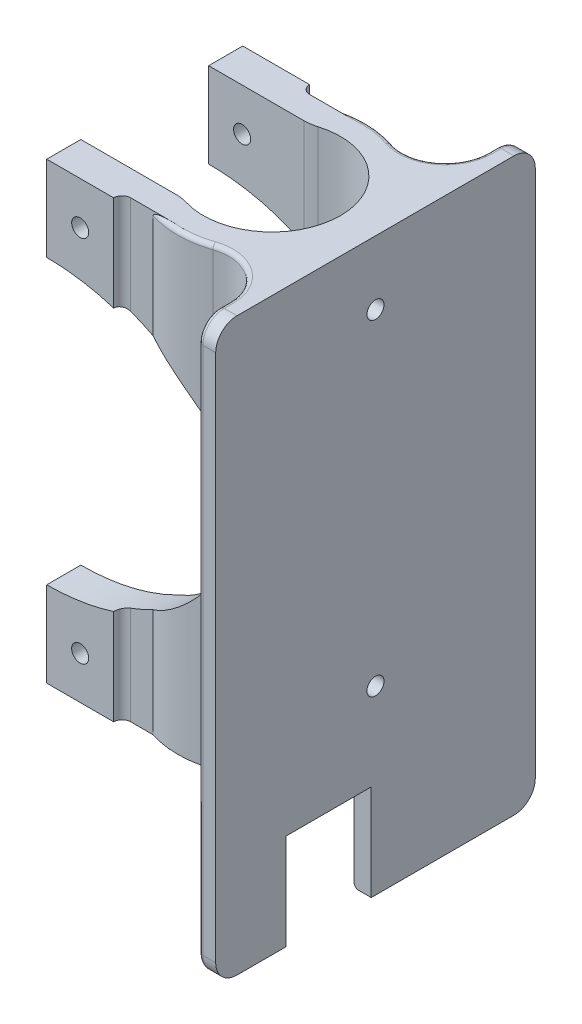
SolidWorks part; units mm, degrees
material "ABS"
ref_plane "Ebene vorne" through (0, 0, 0) normal (0, 0, 1) x (1, 0, 0)
ref_plane "Ebene oben" through (0, 0, 0) normal (0, 1, 0) x (1, 0, 0)
ref_plane "Ebene rechts" through (0, 0, 0) normal (1, 0, 0) x (0, 0, -1)
sketch "Skizze1" plane through (0, 0, 0) normal (0, 1, 0) x (1, 0, 0)
  line L0 (0, -37.5) -> (0, 37.5)
  line L1 (-42.45, 26.5) -> (-50.15, 26.5) construction
  line L2 (-7.2, 3.85) -> (-4, 3.85) construction
  line L3 (-7.2, 3.85) -> (-7.2, -3.85) construction
  line L4 (-7.2, -3.85) -> (-4, -3.85) construction
  line L5 (-4, 3.85) -> (-4, -3.85) construction
  line L6 (-7.2, 3.85) -> (-8.2, 3.85) construction
  line L7 (-7.2, 3.85) -> (-7.2, -3.85) construction
  line L8 (-7.2, -3.85) -> (-8.2, -3.85) construction
  line L9 (-8.2, 3.85) -> (-8.2, -3.85) construction
  line L10 (-52.3, 13) -> (-40.3, 13) construction
  line L11 (-52.3, 13) -> (-52.3, -13) construction
  line L12 (-52.3, -13) -> (-40.3, -13) construction
  line L13 (-40.3, 13) -> (-40.3, -13) construction
  line L14 (-42.45, 26.5) -> (-42.45, 23.3) construction
  line L15 (-42.45, 23.3) -> (-50.15, 23.3) construction
  line L16 (-50.15, 26.5) -> (-50.15, 23.3) construction
  line L17 (-40.3, 13) -> (-33.6274, 13) construction
  line L18 (-50.1, -23) -> (-42.5, -23) construction
  line L19 (-50.1, -23) -> (-50.1, -24.95) construction
  line L20 (-50.1, -24.95) -> (-42.5, -24.95) construction
  line L21 (-42.5, -23) -> (-42.5, -24.95) construction
  line L22 (-48.3, -23) -> (-44.3, -23) construction
  line L23 (-48.3, -23) -> (-48.3, 27) construction
  line L24 (-48.3, 27) -> (-44.3, 27) construction
  line L25 (-44.3, -23) -> (-44.3, 27) construction
  line L26 (-40.3, -13) -> (-33.6274, -13) construction
  line L27 (-30.1489, -15) -> (-54.15, -15)
  line L28 (-54.15, -15) -> (-54.15, -23)
  line L29 (-54.15, -23) -> (-38.45, -23)
  line L30 (-30.1489, 15) -> (-54.15, 15)
  line L31 (-54.15, 15) -> (-54.15, 23)
  line L32 (-54.15, 23) -> (-38.45, 23)
  line L33 (-38.45, 23) -> (-38.45, 21)
  line L34 (-38.45, 21) -> (-31.1855, 21)
  line L35 (-38.45, -23) -> (-38.45, -21)
  line L36 (-38.45, -21) -> (-31.1855, -21)
  line L37 (0, 37.5) -> (-4, 37.5)
  line L38 (-4, 37.5) -> (-4, 30.4026)
  line L39 (0, -37.5) -> (-4, -37.5)
  line L40 (-4, -37.5) -> (-4, -30.4026)
  line L42 (-52.3, 13) -> (-54.15, 13) construction
  line L43 (-52.3, 13) -> (-52.3, -13) construction
  line L44 (-52.3, -13) -> (-54.15, -13) construction
  line L45 (-54.15, 13) -> (-54.15, -13) construction
  circle A0 centre (-24.3, 0) radius 16 construction
  arc A1 (-30.1489, 15) -> (-30.1489, -15) centre (-24.3, 0) cw
  arc A2 (-31.1855, 21) -> (-17.2087, 20.9314) centre (-24.3, 0) cw
  arc A3 (-17.2087, -20.9314) -> (-31.1855, -21) centre (-24.3, 0) cw
  arc A4 (-4, 30.4026) -> (-17.2087, 20.9314) centre (-14, 30.4026) cw
  arc A5 (-4, -30.4026) -> (-17.2087, -20.9314) centre (-14, -30.4026) ccw
  point P3 (0, 0)
  point P6 (-4, 0)
  point P25 (-46.3, 23.3)
  point P26 (-46.3, 13)
  point P33 (-46.3, 27)
  point P34 (-46.3, -24.95)
  point P38 (-46.3, -13)
  point P39 (-46.3, 26.5)
  point P40 (-52.3, 0)
  point P49 (-46.3, 23)
  point P51 (-24.3, 16)
  point P62 (-4, -8.7361)
  dimension "D2" = 3.2
  dimension "D4" = 32
  dimension "D18" = 0.1
  dimension "D22" = 1
  dimension "D24" = 6
  dimension "D26" = 10
  dimension "D1" = 75
  dimension "D3" = 7.7
  dimension "D5" = 4
  dimension "D6" = 1
  dimension "D7" = 4
  dimension "D8" = 26
  dimension "D9" = 3.2
  dimension "D10" = 7.7
  dimension "D11" = 7.6
  dimension "D12" = 1.95
  dimension "D13" = 50
  dimension "D14" = 4
  dimension "D15" = 6
  dimension "D16" = 0.5
  dimension "D17" = 2
  dimension "D19" = 6
  dimension "D20" = 4
  dimension "D21" = 2
  dimension "D23" = 2
  dimension "D25" = 4
  dimension "D27" = 13.85
  dimension "D28" = 22
extrude "Aufsatz-Linear austragen1" add sketch "Skizze1" along normal blind 106.5
sketch "Skizze2" plane through (0, 0, -23) normal (0, 0, -1) x (-1, 0, 0)
  line L0 (38.45, 106.5) -> (54.15, 106.5) construction
  line L1 (44.1349, 100.25) -> (41.9699, 96.5)
  line L2 (41.9699, 96.5) -> (44.1349, 92.75)
  line L3 (44.1349, 92.75) -> (48.4651, 92.75)
  line L4 (48.4651, 92.75) -> (50.6301, 96.5)
  line L5 (50.6301, 96.5) -> (48.4651, 100.25)
  line L6 (48.4651, 100.25) -> (44.1349, 100.25)
  line L7 (44.1349, 13.75) -> (41.9699, 10)
  line L8 (41.9699, 10) -> (44.1349, 6.25)
  line L9 (44.1349, 6.25) -> (48.4651, 6.25)
  line L10 (48.4651, 6.25) -> (50.6301, 10)
  line L11 (50.6301, 10) -> (48.4651, 13.75)
  line L12 (48.4651, 13.75) -> (44.1349, 13.75)
  line L13 (44.1349, 100.25) -> (44.1349, 13.75) construction
  line L14 (38.45, 0) -> (54.15, 0) construction
  circle A0 centre (46.3, 96.5) radius 3.75 construction
  circle A1 centre (46.3, 10) radius 3.75 construction
  point P11 (46.3, 106.5)
  dimension "D1" = 7.5
  dimension "D2" = 10
  dimension "D4" = 10
  dimension "D3" = 2
extrude "Schnitt-Linear austragen1" cut sketch "Skizze2" against normal blind 4.2
sketch "Skizze3" plane through (0, 0, -23) normal (0, 0, -1) x (-1, 0, 0)
  line L0 (48.4651, 100.25) -> (44.1349, 100.25) construction
  circle A0 centre (46.3, 96.5) radius 2
  circle A1 centre (46.3, 10) radius 2
  point P7 (46.3, 100.25)
  dimension "D1" = 4
  dimension "D2" = 4
extrude "Schnitt-Linear austragen2" cut sketch "Skizze3" against normal through all
ref_plane "Ebene1" through (-8.2, 0, 0) normal (-1, 0, 0) x (0, 0, 1)
sketch "Skizze4" plane through (-8.2, 0, 0) normal (-1, 0, 0) x (0, 0, 1)
  line L0 (0, -29.7825) -> (0, 29.7825) construction
  line L7 (37.5, 106.5) -> (-37.5, 106.5) construction
  line L14 (-16.1, 0) -> (16.1, 0) construction
  circle A1 centre (0, 91.5) radius 4
  circle A2 centre (0, 15) radius 4
  point P1 (0, 0)
  point P4 (0, 0)
  dimension "D1" = 8
  dimension "D2" = 15
  dimension "D3" = 15
extrude "Schnitt-Linear austragen3" cut sketch "Skizze4" against normal blind 4.2 and the other way up to next
sketch "Skizze5" plane through (-8.2, 0, 0) normal (-1, 0, 0) x (0, 0, 1)
  circle A0 centre (0, 91.5) radius 2
  circle A1 centre (0, 15) radius 2
  circle A3 centre (0, 91.5) radius 4 construction
  circle A4 centre (0, 15) radius 4 construction
  point P4 (0, 0)
  point P5 (0, 0)
  point P10 (8.0325, 85.3007)
  point P14 (0, 8.8764)
  dimension "D1" = 4
extrude "Schnitt-Linear austragen4" cut sketch "Skizze5" against normal through all
fillet "Verrundung1" radius 10 2 edges at (-30.1489, 53.25, 15) (-30.1489, 53.25, -15)
fillet "Verrundung2" radius 2 2 edges at (-38.45, 53.25, -21) (-38.45, 53.25, 21)
sketch "Skizze6" plane through (0, 0, 0) normal (0, 0, 1) x (1, 0, 0)
  line L0 (-54.15, 106.5) -> (-54.15, 0) construction
  line L1 (-8.2, 40.7) -> (-8.2, -40.7) construction
  line L2 (-54.15, 106.5) -> (-38.45, 106.5) construction
  ellipse E0 centre (-54.15, 53.25) end of major axis (-12.2, 53.25) minor radius 33.25
  point P10 (-54.15, 53.25)
  dimension "D1" = 4
  dimension "D2" = 20
extrude "Schnitt-Linear austragen5" cut sketch "Skizze6" against normal through all both and the other way through all
sketch "Skizze7" plane through (0, 0, 0) normal (0, -1, 0) x (1, 0, 0)
  line L0 (0, 37.5) -> (0, -37.5)
  line L1 (0, -37.5) -> (-4, -37.5)
  line L2 (-4, -37.5) -> (-4, 37.5)
  line L3 (-4, 37.5) -> (0, 37.5)
extrude "Aufsatz-Linear austragen2" add sketch "Skizze7" along normal blind 27.5
sketch "Skizze8" plane through (0, 0, 0) normal (1, 0, 0) x (0, 0, -1)
  line L0 (37.5, -27.5) -> (-37.5, -27.5) construction
  line L1 (-21, -27.5) -> (-1, -27.5)
  line L2 (-21, -27.5) -> (-21, -5)
  line L3 (-21, -5) -> (-1, -5)
  line L4 (-1, -27.5) -> (-1, -5)
  line L5 (-37.5, 106.5) -> (-37.5, -27.5) construction
  dimension "D1" = 16.5
  dimension "D2" = 20
  dimension "D3" = 22.5
extrude "Schnitt-Linear austragen6" cut sketch "Skizze8" against normal through all
fillet "Verrundung4" radius 10 1 edges at (-4, 0, 0)
fillet "Verrundung5" radius 5 4 edges at (-2, -27.5, -37.5) (-2, 106.5, -37.5) (-2, -27.5, 37.5) (-2, 106.5, 37.5)
fillet "Verrundung6" radius 1 14 edges at (-8.1728, 106.5, -22.2759) (-4, -27.5, -15.75) (-24.1915, 106.5, -22.0997) (-4, 39.5, -37.5) (-4, 106.5, -31.4513) (-4, 105.0355, -36.0355) (-4, -26.0355, -36.0355) (-4, -27.5, 26.75) (-4, 39.5, 37.5) (-4, 105.0355, 36.0355) (-4, -26.0355, 36.0355) (-24.1915, 106.5, 22.0997) (-8.1728, 106.5, 22.2759) (-4, 106.5, 31.4513)
